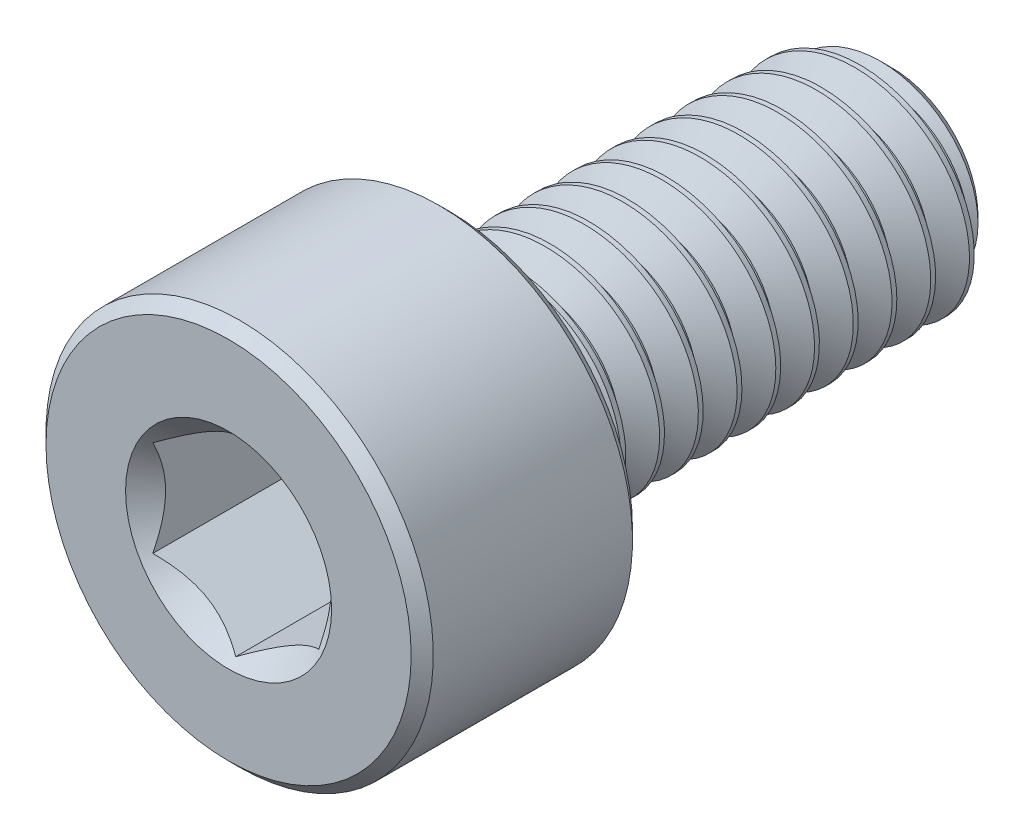
SolidWorks part; units mm, degrees
ref_plane "Front Plane" through (0, 0, 0) normal (0, 0, 1) x (1, 0, 0)
ref_plane "Top Plane" through (0, 0, 0) normal (0, 1, 0) x (1, 0, 0)
ref_plane "Right Plane" through (0, 0, 0) normal (1, 0, 0) x (0, 0, -1)
sketch "Sketch1" plane through (0, 0, 0) normal (1, 0, 0) x (0, 0, -1)
  line L0 (-6, 0) -> (6, 0) construction
  line L1 (6, 0) -> (6, 1.5453) construction
  line L2 (6, 1.5453) -> (5.5453, 2) construction
  line L3 (5.5453, 2) -> (5.475, 2) construction
  line L4 (5.475, 2) -> (-2, 2) construction
  line L5 (-2, 2) -> (-2, 3.5) construction
  line L6 (-2, 3.5) -> (-6, 3.5) construction
  line L7 (-6, 3.5) -> (-6, 0) construction
  line L8 (6, 1.5453) -> (6, 2) construction
  line L9 (5.9562, 2.0758) -> (6.3062, 1.4696) construction
  line L10 (6.3062, 1.4696) -> (6.6562, 2.0758) construction
  line L11 (6.6562, 2.0758) -> (5.9562, 2.0758) construction
  line L12 (6.3062, 2.0758) -> (6.3062, 2) construction
  line L13 (6.3062, 1.4696) -> (6.3062, 1.5453) construction
  line L14 (6.2625, 1.5453) -> (6.35, 1.5453) construction
  line L15 (6, 2) -> (6.6125, 2) construction
  line L16 (5.9781, 2.0379) -> (6.6344, 2.0379) construction
  line L17 (6, 0) -> (6, -2) construction
  line L18 (-2.2, 3.5) -> (-2, 3.3) construction
  line L19 (-5.8, 3.5) -> (-6, 3.3) construction
  line L20 (-2, 2) -> (-2, 0) construction
  line L21 (-2, 1) -> (0.6667, 1) construction
  line L22 (0.6667, 1) -> (3.3333, 1) construction
  line L23 (3.3333, 1) -> (6, 1) construction
  line L24 (0.6667, 1) -> (0.6667, 2) construction
  line L25 (0.6667, 2) -> (0.6667, 3.5) construction
  line L26 (3.3333, 1) -> (3.3333, 3.5) construction
  point P0 (-6, 1.5)
  point P3 (4.25, 2)
  point P4 (0, 0)
  point P18 (3.3333, 2)
  point P22 (6.3062, 1.5453)
  point P24 (5.475, 2)
  point P25 (6.3062, 2)
  point P28 (6.3062, 2.0379)
  point P29 (4.25, -2)
  point P30 (0.6667, 2)
  point P31 (-4, 3.5)
  point P37 (-2.7, 3.5)
  point P38 (-5.7, 3.5)
  point P45 (0.6667, 1)
  point P46 (3.3333, 1)
  dimension "D2" = 0.0875
  dimension "D7" = 0.2
  dimension "D8" = 0.2
  dimension "D9" = 0.2
  dimension "D10" = 0.1
  dimension "D11" = 0.5
  dimension "Drive Size" = 3
  dimension "Head Diameter" = 7
  dimension "Head Height" = 4
  dimension "Thread Pitch" = 0.7
  dimension "Thread Dia" = 4
  dimension "Length" = 8
  dimension "D12" = 0.525
  dimension "D4" = 1.75
  dimension "D3" = 45
sketch "Sketch2" plane through (0, 0, 0) normal (1, 0, 0) x (0, 0, -1)
  line L0 (-6, 0) -> (-6, 3.3)
  line L1 (-5.8, 3.5) -> (-2.2, 3.5)
  line L2 (-2, 3.3) -> (-2, 2.2)
  line L4 (5.5453, 2) -> (6, 1.5453)
  line L5 (6, 1.5453) -> (6, 0)
  line L6 (-2, 3.5) -> (-6, 3.5) construction
  line L7 (6, 0) -> (-6, 0)
  line L8 (-5.8, 3.5) -> (-6, 3.3) construction
  line L10 (-5.8, 3.5) -> (-6, 3.3)
  line L14 (-2.2, 3.5) -> (-2, 3.3) construction
  line L16 (-2.2, 3.5) -> (-2, 3.3)
  line L17 (-2, 2) -> (-2, 3.5) construction
  line L19 (-1.8, 2) -> (5.5453, 2)
  line L20 (5.475, 2) -> (-2, 2) construction
  arc A1 (-2, 2.2) -> (-1.8, 2) centre (-1.8, 2.2) ccw
  dimension "D3" = 0.2
revolve "Revolve1" add sketch "Sketch2" angle 360 about L7
sketch "Sketch3" plane through (0, 0, 6) normal (0, 0, 1) x (1, 0, 0)
  line L1 (1.5, -0.866) -> (1.5, 0.866)
  line L2 (1.5, 0.866) -> (0, 1.7321)
  line L3 (0, 1.7321) -> (-1.5, 0.866)
  line L4 (-1.5, 0.866) -> (-1.5, -0.866)
  line L5 (-1.5, -0.866) -> (0, -1.7321)
  line L6 (0, -1.7321) -> (1.5, -0.866)
  circle A0 centre (0, 0) radius 1.5 construction
  circle A1 centre (0, 0) radius 3.5 construction
  circle A2 centre (0, 0) radius 3.5 construction
  circle A3 centre (0, 0) radius 1.7321 construction
  point P13 (0, 0)
  dimension "D1" = 3.4641
extrude "Cut-Extrude1" cut sketch "Sketch3" against normal offset from surface (3 mm away) 1 up to face at (0, 3.3, 2)
sketch "Sketch4" plane through (0, 0, 6) normal (0, 0, 1) x (1, 0, 0)
  circle A0 centre (0, 0) radius 1.862
  dimension "D1" = 3.7239
extrude "Cut-Extrude2" cut sketch "Sketch4" against normal up to vertex (2 mm away) draft 45 up to point (0, 3.5, 4)
sketch "Sketch11" plane through (0, 0, 0) normal (1, 0, 0) x (0, 0, -1)
  line L0 (-6, 0) -> (6, 0) construction
  line L1 (-6, 0) -> (6, 0) construction
  line L2 (-0.5, 0) -> (-0.5, 2) construction
  line L3 (5.475, 2) -> (-2, 2) construction
  line L4 (4.5, 0) -> (4.5, 2) construction
  line L6 (6, 1.5453) -> (6, 2) construction
  point P2 (-0.5, 0)
  point P3 (4.5, 0)
  dimension "D1" = 1.5
  dimension "D2" = 1.5
sketch "Sketch6" plane through (0, 0, -6) normal (0, 0, -1) x (-1, 0, 0)
  circle A0 centre (0, 0) radius 2
curve "Helix/Spiral1" pitch 0.7 height 8.7 radius 2 centre (0, 0, -6) axis (0, 0, 1) start towards (0, 1, 0)
sketch "Sketch10" plane through (0, 0, 0) normal (1, 0, 0) x (0, 0, -1)
  line L0 (-1.8, -3.5) -> (-1.8, 3.5)
  line L5 (-6, 0) -> (6, 0) construction
  line L6 (-1.8, 2) -> (-1.8, -2) construction
  point P3 (-1.8, 0)
split "Split1" trim tools "Sketch10" bodies to split 106 resulting bodies 114 115
sketch "Sketch7" plane through (0, 0, 0) normal (1, 0, 0) x (0, 0, -1)
  line L0 (5.9781, 2.0379) -> (6.6344, 2.0379)
  line L1 (6.6344, 2.0379) -> (6.35, 1.5453)
  line L2 (6.35, 1.5453) -> (6.2625, 1.5453)
  line L3 (6.2625, 1.5453) -> (5.9781, 2.0379)
sweep "Cut-Sweep1" cut profiles "Sketch7" path "Helix/Spiral1" align with end faces yes
sketch "Sketch8" plane through (0, 0, 0) normal (1, 0, 0) x (0, 0, -1)
  line L0 (-2, 0) -> (-2, 2)
  line L1 (-1.8, -2) -> (-1.8, 2) construction
  line L2 (-2, 2) -> (-1.8, 2)
  line L4 (-1.8, 2) -> (-0.6453, 0)
  line L5 (-0.6453, 0) -> (-2, 0)
  line L6 (5.475, 2) -> (-2, 2) construction
  line L7 (-6, 0) -> (6, 0) construction
  dimension "D1" = 60
revolve "Revolve2" add sketch "Sketch8" angle 360 about L5
equation "\"D2@Sketch1\" = \"Thread Pitch@Sketch1\" / 8"
equation "\"D4@Helix/Spiral1\" = \"Thread Pitch@Sketch1\""
equation "\"D7@Sketch1\" = \"Head Height@Sketch1\" * .05"
equation "\"D8@Sketch1\"=\"D7@Sketch1\""
equation "\"D9@Sketch1\"=\"D7@Sketch1\""
equation "\"D10@Sketch1\"=\"D7@Sketch1\"/2"
equation "\"D11@Sketch1\"=\"D10@Sketch1\"*5"
equation "\"D4@Sketch1\"=\"Thread Pitch@Sketch1\"*2.5"
equation "\"D12@Sketch1\"=\"Thread Pitch@Sketch1\"*.75"
equation "\"D3@Helix/Spiral1\"=\"Length@Sketch1\"+\"Thread Pitch@Sketch1\""
equation "\"D3@Sketch2\"=\"Thread Dia@Sketch1\"*0.05"
equation "\"D1@Sketch11\"=\"Length@Sketch1\"*0.1875"
equation "\"D2@Sketch11\"=\"D1@Sketch11\""
equation "\"D1@Sketch4\"=\"D1@Sketch3\"*1.075"
